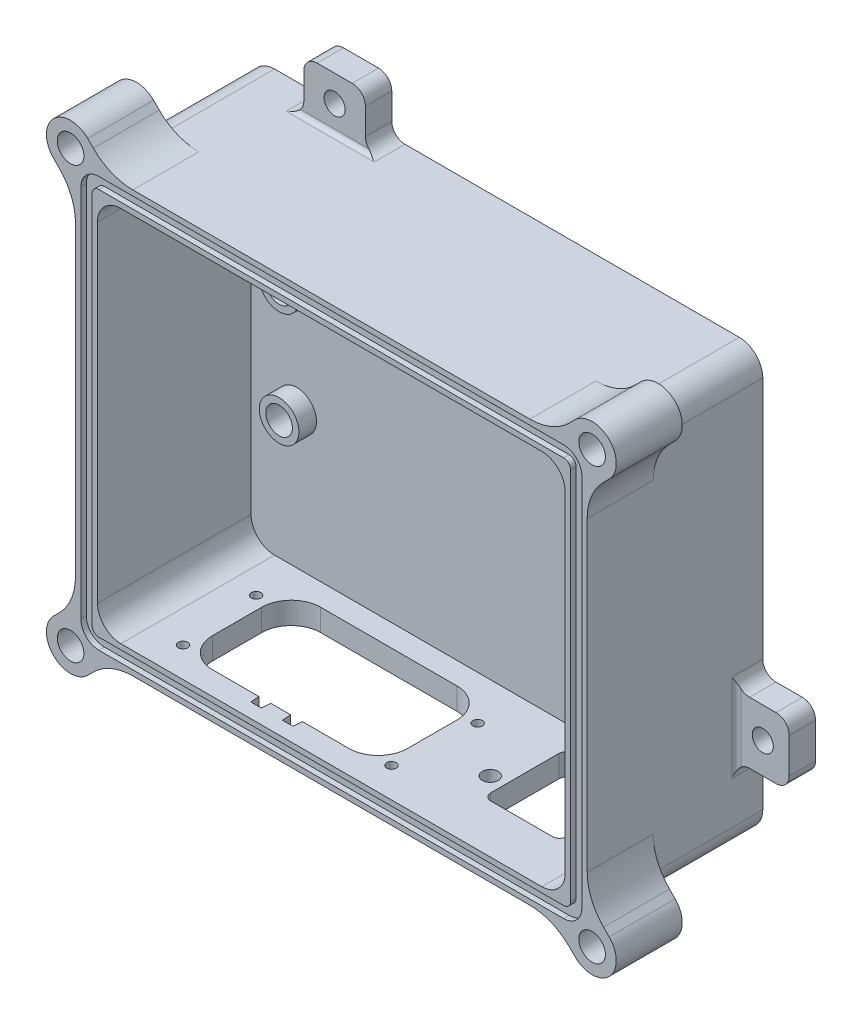
SolidWorks part; units mm, degrees
material "ABS"
ref_plane "X-Y Datum" through (0, 0, 0) normal (0, 0, 1) x (1, 0, 0)
ref_plane "X-Z Datum" through (0, 0, 0) normal (0, 1, 0) x (1, 0, 0)
ref_plane "Y-Z Datum" through (0, 0, 0) normal (1, 0, 0) x (0, 0, -1)
sketch "Sketch1" plane through (0, 0, 0) normal (0, 0, 1) x (1, 0, 0)
  line L1 (-53.1813, 42.8625) -> (53.1812, 42.8625)
  line L2 (-53.1813, 42.8625) -> (-53.1812, -42.8625)
  line L3 (-53.1812, -42.8625) -> (53.1813, -42.8625)
  line L4 (53.1812, 42.8625) -> (53.1813, -42.8625)
  line L5 (-53.1813, 42.8625) -> (53.1813, -42.8625) construction
  line L6 (-53.1812, -42.8625) -> (53.1812, 42.8625) construction
  point P0 (0, 0)
  dimension "D1" = 106.3625
  dimension "D2" = 85.725
extrude "Boss-Extrude1" add sketch "Sketch1" along normal blind 34.925
shell "Shell1" thickness 5 removed face at (0, 0, 34.925) outward yes
fillet "Fillet1" radius 5.334 8 edges at (-58.1812, -47.8625, 14.9625) (58.1813, -47.8625, 14.9625) (53.1812, 42.8625, 17.4625) (58.1812, 47.8625, 14.9625) (-58.1813, 47.8625, 14.9625) (-53.1813, 42.8625, 17.4625) (53.1813, -42.8625, 17.4625) (-53.1812, -42.8625, 17.4625)
sketch "Sketch2" plane through (0, 0, 34.925) normal (0, 0, 1) x (1, 0, 0)
  line L20 (-52.8472, -46.6452) -> (52.8472, -46.6452)
  line L21 (56.9639, -42.5285) -> (56.9639, 42.5285)
  line L22 (52.8472, 46.6452) -> (-52.8473, 46.6452)
  line L23 (-56.9639, 42.5285) -> (-56.9639, -42.5285)
  line L24 (-52.8472, -45.3625) -> (52.8473, -45.3625)
  line L25 (55.6812, -42.5285) -> (55.6812, 42.5285)
  line L26 (52.8472, 45.3625) -> (-52.8473, 45.3625)
  line L27 (-55.6812, 42.5285) -> (-55.6812, -42.5285)
  line L28 (-52.8472, -45.3625) -> (52.8473, -45.3625) construction
  line L29 (55.6812, -42.5285) -> (55.6812, 42.5285) construction
  line L30 (52.8472, 45.3625) -> (-52.8473, 45.3625) construction
  line L31 (-55.6812, 42.5285) -> (-55.6812, -42.5285) construction
  line L32 (-54.3986, 42.5285) -> (-54.3986, -42.5285)
  line L33 (-52.8472, -44.0798) -> (52.8472, -44.0798)
  line L34 (54.3986, -42.5285) -> (54.3986, 42.5285)
  line L35 (52.8472, 44.0798) -> (-52.8473, 44.0798)
  arc A16 (52.8472, -46.6452) -> (56.9639, -42.5285) centre (52.8473, -42.5285) ccw
  arc A17 (56.9639, 42.5285) -> (52.8472, 46.6452) centre (52.8472, 42.5285) ccw
  arc A18 (-52.8473, 46.6452) -> (-56.9639, 42.5285) centre (-52.8473, 42.5285) ccw
  arc A19 (-56.9639, -42.5285) -> (-52.8472, -46.6452) centre (-52.8472, -42.5285) ccw
  arc A20 (-55.6812, -42.5285) -> (-52.8472, -45.3625) centre (-52.8472, -42.5285) ccw
  arc A21 (52.8473, -45.3625) -> (55.6812, -42.5285) centre (52.8473, -42.5285) ccw
  arc A22 (55.6812, 42.5285) -> (52.8472, 45.3625) centre (52.8472, 42.5285) ccw
  arc A23 (-52.8473, 45.3625) -> (-55.6812, 42.5285) centre (-52.8473, 42.5285) ccw
  arc A24 (-55.6812, -42.5285) -> (-52.8472, -45.3625) centre (-52.8472, -42.5285) ccw construction
  arc A25 (52.8473, -45.3625) -> (55.6812, -42.5285) centre (52.8473, -42.5285) ccw construction
  arc A26 (55.6812, 42.5285) -> (52.8472, 45.3625) centre (52.8472, 42.5285) ccw construction
  arc A27 (-52.8473, 45.3625) -> (-55.6812, 42.5285) centre (-52.8473, 42.5285) ccw construction
  arc A28 (-52.8473, 44.0798) -> (-54.3986, 42.5285) centre (-52.8473, 42.5285) ccw
  arc A29 (-54.3986, -42.5285) -> (-52.8472, -44.0798) centre (-52.8472, -42.5285) ccw
  arc A30 (52.8472, -44.0798) -> (54.3986, -42.5285) centre (52.8473, -42.5285) ccw
  arc A31 (54.3986, 42.5285) -> (52.8472, 44.0798) centre (52.8472, 42.5285) ccw
  dimension "D4" = 2.5654
  dimension "D1" = 2.5
  dimension "D2" = 1.2827
  dimension "D3" = 1.2827
extrude "Cut-Extrude1" cut sketch "Sketch2" against normal blind 1.2446
sketch "Sketch4" plane through (0, 0, 34.925) normal (0, 0, 1) x (1, 0, 0)
  line L4 (58.1813, -42.5285) -> (58.1812, 42.5285) construction
  line L6 (47.8473, -37.5285) -> (59.2937, -48.975)
  line L7 (55.4046, -52.8641) -> (50.4031, -47.8625)
  line L8 (-52.8472, -47.8625) -> (52.8473, -47.8625) construction
  line L9 (63.1828, -45.0859) -> (58.1813, -40.0843)
  line L10 (-52.8472, -47.8625) -> (52.8473, -47.8625)
  line L11 (58.1813, -42.5285) -> (58.1812, 42.5285)
  arc A2 (47.8473, -42.8625) -> (53.1813, -37.5285) centre (47.8473, -37.5285) ccw construction
  circle A3 centre (59.2937, -48.975) radius 3.025
  circle A4 centre (59.2937, -48.975) radius 5.5
  arc A5 (52.8472, -46.6452) -> (56.9639, -42.5285) centre (52.8473, -42.5285) ccw construction
  arc A6 (52.8473, -47.8625) -> (58.1813, -42.5285) centre (52.8473, -42.5285) ccw construction
  arc A7 (58.1812, 42.5285) -> (52.8472, 47.8625) centre (52.8472, 42.5285) ccw construction
  arc A8 (52.8473, -47.8625) -> (58.1813, -42.5285) centre (52.8473, -42.5285) ccw
  arc A9 (58.1812, 42.5285) -> (52.8472, 47.8625) centre (52.8472, 42.5285) ccw
  point P14 (51.619, -41.3002)
  point P23 (55.7582, -45.4394)
  dimension "D1" = 11
  dimension "D2" = 6.05
  dimension "D4" = 5
extrude "Boss-Extrude2" add sketch "Sketch4" against normal blind 15 separate body contours A9 L11 | A9 | A8 A4 L9 L11 | A8 L10 L7 A4 | A8 A4 A3 | A3 | L11 region at (60.4186, -46.2593, 34.925) region at (57.6777, -45.1365, 34.925) region at (59.5123, -42.505, 34.925) region at (52.8237, -49.1935, 34.925)
sketch "Sketch5" plane through (0, 0, 34.925) normal (0, 0, 1) x (1, 0, 0)
  line L3 (-52.8472, -47.8625) -> (52.8473, -47.8625) construction
  line L4 (63.1828, -45.0859) -> (58.1813, -40.0843) construction
  line L5 (55.4046, -52.8641) -> (50.4031, -47.8625) construction
  line L6 (47.8473, -37.5285) -> (59.2937, -48.975) construction
  line L10 (-52.8472, -47.8625) -> (52.8473, -47.8625)
  line L11 (63.1828, -45.0859) -> (58.1813, -40.0843)
  line L12 (55.4046, -52.8641) -> (50.4031, -47.8625)
  line L13 (47.8473, -37.5285) -> (59.2937, -48.975)
  circle A1 centre (59.2937, -48.975) radius 3.025
  circle A2 centre (59.2937, -48.975) radius 3.025
  circle A7 centre (59.2937, -48.975) radius 5.5
  circle A8 centre (59.2937, -48.975) radius 5.5
  arc A9 (52.8473, -47.8625) -> (58.1813, -42.5285) centre (52.8473, -42.5285) ccw construction
  arc A11 (52.8473, -47.8625) -> (58.1813, -42.5285) centre (52.8473, -42.5285) ccw
  dimension "D1" = 0
  dimension "D4" = 0
extrude "Cut-Extrude4" cut sketch "Sketch5" against normal blind 8 contours A2 region at (60.4186, -46.2593, 34.925)
mirror "Mirror3" about plane through (0, 0, 0) normal (1, 0, 0) of bodies 107 106
mirror "Mirror7" about plane through (0, 0, 0) normal (0, 1, 0) of bodies 107 109
combine bodies "Combine3" operation type add bodies to combine 102 107 109 121 122
fillet "Fillet2" radius 12.7 8 edges at (-50.4031, -47.8625, 27.425) (-58.1813, -40.0843, 27.425) (50.4031, -47.8625, 27.425) (58.1813, -40.0843, 27.425) (-58.1813, 40.0843, 27.425) (-50.4031, 47.8625, 27.425) (50.4031, 47.8625, 27.425) (58.1813, 40.0843, 27.425)
sketch "Sketch13" plane through (0, -47.8625, 0) normal (0, -1, 0) x (1, 0, 0)
  line L0 (-12.3227, 29.1278) -> (-12.4976, 31.1278) construction
  line L1 (-12.4976, 31.1278) -> (-13.9477, 31.1278) construction
  line L2 (-13.9477, 31.1278) -> (-14.1227, 29.1278) construction
  line L3 (-19.6976, 31.1278) -> (-21.1477, 31.1278) construction
  line L4 (-21.1477, 31.1278) -> (-21.3227, 29.1278) construction
  line L5 (-19.5227, 29.1278) -> (-19.6976, 31.1278) construction
  line L6 (-21.3227, 29.1278) -> (-32.3227, 29.1278) construction
  line L7 (-38.5227, 22.9278) -> (-38.5227, 11.7278) construction
  line L8 (-32.3227, 5.5278) -> (-1.3227, 5.5278) construction
  line L9 (4.8773, 11.7278) -> (4.8773, 22.9278) construction
  line L10 (-1.3227, 29.1278) -> (-12.3227, 29.1278) construction
  line L11 (-14.1227, 29.1278) -> (-19.5227, 29.1278) construction
  line L52 (-12.3227, 29.1278) -> (-12.4976, 31.1278) construction
  line L53 (-12.4976, 31.1278) -> (-13.9477, 31.1278) construction
  line L54 (-13.9477, 31.1278) -> (-14.1227, 29.1278) construction
  line L55 (-19.6976, 31.1278) -> (-21.1477, 31.1278) construction
  line L67 (24.0563, 22.2478) -> (24.0563, 6.6978) construction
  line L80 (-21.1477, 31.1278) -> (-21.3227, 29.1278) construction
  line L81 (-19.5227, 29.1278) -> (-19.6976, 31.1278) construction
  line L82 (-21.3227, 29.1278) -> (-32.3227, 29.1278) construction
  line L83 (-38.5227, 22.9278) -> (-38.5227, 11.7278) construction
  line L84 (-32.3227, 5.5278) -> (-1.3227, 5.5278) construction
  line L85 (4.8773, 11.7278) -> (4.8773, 22.9278) construction
  line L86 (-1.3227, 29.1278) -> (-12.3227, 29.1278) construction
  line L87 (-14.1227, 29.1278) -> (-19.5227, 29.1278) construction
  line L88 (-11.8645, 29.6278) -> (-12.0395, 31.6278)
  line L89 (-12.0395, 31.6278) -> (-14.4059, 31.6278)
  line L90 (-14.4059, 31.6278) -> (-14.5808, 29.6278)
  line L91 (-14.5808, 29.6278) -> (-19.0645, 29.6278)
  line L92 (-19.0645, 29.6278) -> (-19.2395, 31.6278)
  line L93 (-19.2395, 31.6278) -> (-21.6059, 31.6278)
  line L94 (-21.6059, 31.6278) -> (-21.7808, 29.6278)
  line L95 (-21.7808, 29.6278) -> (-32.3227, 29.6278)
  line L96 (-39.0227, 22.9278) -> (-39.0227, 11.7278)
  line L97 (-32.3227, 5.0278) -> (-1.3227, 5.0278)
  line L98 (5.3773, 11.7278) -> (5.3773, 22.9278)
  line L99 (-1.3227, 29.6278) -> (-11.8645, 29.6278)
  line L100 (25.1563, 5.5978) -> (39.2063, 5.5978) construction
  line L101 (40.3063, 6.6978) -> (40.3063, 22.2478) construction
  line L102 (39.2063, 23.3478) -> (25.1563, 23.3478) construction
  line L103 (24.0563, 22.2478) -> (24.0563, 6.6978) construction
  line L104 (25.1563, 5.5978) -> (39.2063, 5.5978) construction
  line L105 (40.3063, 6.6978) -> (40.3063, 22.2478) construction
  line L106 (39.2063, 23.3478) -> (25.1563, 23.3478) construction
  line L107 (23.5563, 22.2478) -> (23.5563, 6.6978)
  line L124 (25.1563, 5.0978) -> (39.2063, 5.0978)
  line L125 (40.8063, 6.6978) -> (40.8063, 22.2478)
  line L126 (39.2063, 23.8478) -> (25.1563, 23.8478)
  arc A0 (24.0563, 6.6978) -> (25.1563, 5.5978) centre (25.1563, 6.6978) ccw construction
  arc A1 (39.2063, 5.5978) -> (40.3063, 6.6978) centre (39.2063, 6.6978) ccw construction
  arc A2 (40.3063, 22.2478) -> (39.2063, 23.3478) centre (39.2063, 22.2478) ccw construction
  arc A3 (25.1563, 23.3478) -> (24.0563, 22.2478) centre (25.1563, 22.2478) ccw construction
  arc A12 (24.0563, 6.6978) -> (25.1563, 5.5978) centre (25.1563, 6.6978) ccw construction
  arc A13 (39.2063, 5.5978) -> (40.3063, 6.6978) centre (39.2063, 6.6978) ccw construction
  arc A14 (40.3063, 22.2478) -> (39.2063, 23.3478) centre (39.2063, 22.2478) ccw construction
  arc A15 (25.1563, 23.3478) -> (24.0563, 22.2478) centre (25.1563, 22.2478) ccw construction
  arc A24 (23.5563, 6.6978) -> (25.1563, 5.0978) centre (25.1563, 6.6978) ccw
  arc A25 (39.2063, 5.0978) -> (40.8063, 6.6978) centre (39.2063, 6.6978) ccw
  arc A26 (40.8063, 22.2478) -> (39.2063, 23.8478) centre (39.2063, 22.2478) ccw
  arc A27 (25.1563, 23.8478) -> (23.5563, 22.2478) centre (25.1563, 22.2478) ccw
  spline S0 degree 3 poles (-32.3227, 29.1278) (-35.9545, 29.1278) (-38.5227, 26.5597) (-38.5227, 22.9278) knots 0 0 0 0 1 1 1 1 weights 1 0.804738 0.804738 1 construction
  spline S1 degree 3 poles (-38.5227, 11.7278) (-38.5227, 8.0959) (-35.9545, 5.5278) (-32.3227, 5.5278) knots 0 0 0 0 1 1 1 1 weights 1 0.804738 0.804738 1 construction
  spline S2 degree 3 poles (-1.3227, 5.5278) (2.3092, 5.5278) (4.8773, 8.0959) (4.8773, 11.7278) knots 0 0 0 0 1 1 1 1 weights 1 0.804738 0.804738 1 construction
  spline S3 degree 3 poles (4.8773, 22.9278) (4.8773, 26.5597) (2.3092, 29.1278) (-1.3227, 29.1278) knots 0 0 0 0 1 1 1 1 weights 1 0.804738 0.804738 1 construction
  spline S4 degree 3 poles (-32.3227, 29.1278) (-35.9545, 29.1278) (-38.5227, 26.5597) (-38.5227, 22.9278) knots 0 0 0 0 1 1 1 1 weights 1 0.804738 0.804738 1 construction
  spline S5 degree 3 poles (-38.5227, 11.7278) (-38.5227, 8.0959) (-35.9545, 5.5278) (-32.3227, 5.5278) knots 0 0 0 0 1 1 1 1 weights 1 0.804738 0.804738 1 construction
  spline S6 degree 3 poles (-1.3227, 5.5278) (2.3092, 5.5278) (4.8773, 8.0959) (4.8773, 11.7278) knots 0 0 0 0 1 1 1 1 weights 1 0.804738 0.804738 1 construction
  spline S7 degree 3 poles (4.8773, 22.9278) (4.8773, 26.5597) (2.3092, 29.1278) (-1.3227, 29.1278) knots 0 0 0 0 1 1 1 1 weights 1 0.804738 0.804738 1 construction
  spline S8 degree 1 poles (-32.3227, 29.6278) (-39.0227, 22.9278) knots 0 0 1 1 construction
  spline S9 degree 1 poles (-39.0227, 11.7278) (-32.3227, 5.0278) knots 0 0 1 1 construction
  spline S10 degree 1 poles (-1.3227, 5.0278) (5.3773, 11.7278) knots 0 0 1 1 construction
  spline S11 degree 1 poles (5.3773, 22.9278) (-1.3227, 29.6278) knots 0 0 1 1 construction
  spline S12 degree 3 poles (-32.3227, 29.6278) (-32.7308, 29.6278) (-33.5306, 29.5573) (-35.22, 29.0854) (-37.2004, 27.8055) (-38.4803, 25.8252) (-38.9522, 24.1358) (-39.0227, 23.3359) (-39.0227, 22.9278) knots 0 0 0 0 0.125 0.25 0.5 0.75 0.875 1 1 1 1
  spline S13 degree 3 poles (-39.0227, 11.7278) (-39.0227, 11.3197) (-38.9522, 10.5199) (-38.4803, 8.8305) (-37.2004, 6.8501) (-35.22, 5.5702) (-33.5306, 5.0983) (-32.7308, 5.0278) (-32.3227, 5.0278) knots 0 0 0 0 0.125 0.25 0.5 0.75 0.875 1 1 1 1
  spline S14 degree 3 poles (-1.3227, 5.0278) (-0.9146, 5.0278) (-0.1147, 5.0983) (1.5747, 5.5702) (3.555, 6.8501) (4.8349, 8.8305) (5.3068, 10.5199) (5.3773, 11.3197) (5.3773, 11.7278) knots 0 0 0 0 0.125 0.25 0.5 0.75 0.875 1 1 1 1
  spline S15 degree 3 poles (5.3773, 22.9278) (5.3773, 23.3359) (5.3068, 24.1358) (4.8349, 25.8252) (3.555, 27.8055) (1.5747, 29.0854) (-0.1147, 29.5573) (-0.9146, 29.6278) (-1.3227, 29.6278) knots 0 0 0 0 0.125 0.25 0.5 0.75 0.875 1 1 1 1
  spline S16 degree 3 poles (-43.1077, 10.0278) (-43.1077, 12.1978) (-40.9377, 12.1978) (-40.9377, 10.0278) knots 0 0 0 0 1 1 1 1 weights 1 0.333333 0.333333 1 construction
  spline S17 degree 3 poles (-40.9377, 10.0278) (-40.9377, 7.8578) (-43.1077, 7.8578) (-43.1077, 10.0278) knots 0 0 0 0 1 1 1 1 weights 1 0.333333 0.333333 1 construction
  spline S18 degree 3 poles (-41.6077, 28.1278) (-41.6077, 30.2978) (-39.4377, 30.2978) (-39.4377, 28.1278) knots 0 0 0 0 1 1 1 1 weights 1 0.333333 0.333333 1 construction
  spline S19 degree 3 poles (-39.4377, 28.1278) (-39.4377, 25.9578) (-41.6077, 25.9578) (-41.6077, 28.1278) knots 0 0 0 0 1 1 1 1 weights 1 0.333333 0.333333 1 construction
  spline S20 degree 3 poles (-43.1077, 10.0278) (-43.1077, 12.1978) (-40.9377, 12.1978) (-40.9377, 10.0278) knots 0 0 0 0 1 1 1 1 weights 1 0.333333 0.333333 1
  spline S21 degree 3 poles (-40.9377, 10.0278) (-40.9377, 7.8578) (-43.1077, 7.8578) (-43.1077, 10.0278) knots 0 0 0 0 1 1 1 1 weights 1 0.333333 0.333333 1
  spline S22 degree 3 poles (-41.6077, 28.1278) (-41.6077, 30.2978) (-39.4377, 30.2978) (-39.4377, 28.1278) knots 0 0 0 0 1 1 1 1 weights 1 0.333333 0.333333 1
  spline S23 degree 3 poles (-39.4377, 28.1278) (-39.4377, 25.9578) (-41.6077, 25.9578) (-41.6077, 28.1278) knots 0 0 0 0 1 1 1 1 weights 1 0.333333 0.333333 1
  spline S24 degree 3 poles (7.9623, 28.1278) (7.9623, 25.9578) (5.7923, 25.9578) (5.7923, 28.1278) knots 0 0 0 0 1 1 1 1 weights 1 0.333333 0.333333 1 construction
  spline S25 degree 3 poles (5.7923, 28.1278) (5.7923, 30.2978) (7.9623, 30.2978) (7.9623, 28.1278) knots 0 0 0 0 1 1 1 1 weights 1 0.333333 0.333333 1 construction
  spline S26 degree 3 poles (7.9623, 28.1278) (7.9623, 25.9578) (5.7923, 25.9578) (5.7923, 28.1278) knots 0 0 0 0 1 1 1 1 weights 1 0.333333 0.333333 1
  spline S27 degree 3 poles (5.7923, 28.1278) (5.7923, 30.2978) (7.9623, 30.2978) (7.9623, 28.1278) knots 0 0 0 0 1 1 1 1 weights 1 0.333333 0.333333 1
  spline S28 degree 3 poles (9.4623, 10.0278) (9.4623, 7.8578) (7.2923, 7.8578) (7.2923, 10.0278) knots 0 0 0 0 1 1 1 1 weights 1 0.333333 0.333333 1 construction
  spline S29 degree 3 poles (7.2923, 10.0278) (7.2923, 12.1978) (9.4623, 12.1978) (9.4623, 10.0278) knots 0 0 0 0 1 1 1 1 weights 1 0.333333 0.333333 1 construction
  spline S30 degree 3 poles (7.2923, 10.0278) (7.2923, 12.1978) (9.4623, 12.1978) (9.4623, 10.0278) knots 0 0 0 0 1 1 1 1 weights 1 0.333333 0.333333 1
  spline S31 degree 3 poles (9.4623, 10.0278) (9.4623, 7.8578) (7.2923, 7.8578) (7.2923, 10.0278) knots 0 0 0 0 1 1 1 1 weights 1 0.333333 0.333333 1
  point P47 (20.1813, 18.9728)
  point P48 (44.1813, 9.9728)
  dimension "D1" = 0.5
  dimension "D2" = 0.5
extrude "Cut-Extrude6" cut sketch "Sketch13" against normal blind 5 contours L126 A27 L107 A24 L124 A25 L125 A26 | L98 S15 L99 L88 L89 L90 L91 L92 L93 L94 L95 S12 L96 S13 L97 S14 | S27 S26 | S31 S30 | S23 S22 | S21 S20 region at (-16.8227, -47.8625, 17.4547) region at (32.1813, -47.8625, 14.4728) region at (-42.0227, -47.8625, 10.0278) region at (-40.5227, -47.8625, 28.1278) region at (6.8773, -47.8625, 28.1278) region at (8.3773, -47.8625, 10.0278)
hole_wizard "M3 Clearance Hole1" positions "Sketch17" profile "Sketch15" hole size "M3" standard "ANSI Metric"
sketch "Sketch17" plane through (0, -47.8625, 0) normal (0, -1, 0) x (-1, 0, 0)
  point P10 (-20.1813, -18.9728)
  point P13 (-44.1813, -9.9728)
sketch "Sketch15" plane through (20.1813, -47.8625, 18.9728) normal (1, 0, 0) x (0, 0, -1)
  line L0 (0, 0) -> (0, 6.0815)
  line L1 (0, 6.0815) -> (1.8, 5)
  line L2 (1.8, 5) -> (1.8, 0)
  line L5 (1.8, 0) -> (0, 0)
  line L10 (0, 6.0815) -> (-1.8, 5) construction
  line L11 (0, -6.35) -> (0, 107.95) construction
  dimension "Hole Dia." = 3.6
  dimension "Hole Depth" = 5
  dimension "Drill Angle" = 118
sketch "Sketch18" plane through (0, 0, 0) normal (0, 0, 1) x (1, 0, 0)
  circle A0 centre (-42.8028, 14.0785) radius 3.025
  circle A1 centre (-42.8028, -11.8295) radius 3.025
  circle A2 centre (28.9332, -12.9535) radius 3.025
  circle A3 centre (28.9332, 14.9865) radius 3.025
  circle A4 centre (-42.8028, 14.0785) radius 4.5
  circle A5 centre (-42.8028, -11.8295) radius 4.5
  circle A6 centre (28.9332, 14.9865) radius 4.5
  circle A7 centre (28.9332, -12.9535) radius 4.5
  point P0 (-42.8028, 14.0785)
  point P1 (-42.8028, -11.8295)
  point P3 (28.9332, -12.9535)
  point P5 (28.9332, 14.9865)
  dimension "D1" = 6.05
  dimension "D2" = 9
extrude "Boss-Extrude3" add sketch "Sketch18" along normal blind 4
sketch "Sketch19" plane through (0, 0, 0) normal (0, 0, 1) x (1, 0, 0)
  circle A0 centre (28.9332, 14.9865) radius 3.025 construction
  circle A1 centre (28.9332, -12.9535) radius 3.025 construction
  circle A2 centre (-42.8028, -11.8295) radius 3.025 construction
  circle A3 centre (-42.8028, 14.0785) radius 3.025 construction
  circle A4 centre (28.9332, 14.9865) radius 3.025
  circle A5 centre (28.9332, -12.9535) radius 3.025
  circle A6 centre (-42.8028, -11.8295) radius 3.025
  circle A7 centre (-42.8028, 14.0785) radius 3.025
extrude "Cut-Extrude7" cut sketch "Sketch19" against normal blind 1.5
sketch "Sketch20" plane through (0, 0, -5) normal (0, 0, -1) x (-1, 0, 0)
  line L0 (-45.1426, 47.8625) -> (45.1426, 47.8625) construction
  line L1 (40.1812, 47.8625) -> (26.1813, 47.8625)
  line L2 (40.1812, 47.8625) -> (40.1812, 59.8625)
  line L3 (40.1812, 59.8625) -> (26.1813, 59.8625)
  line L4 (26.1813, 47.8625) -> (26.1813, 59.8625)
  line L5 (-58.1813, -34.8238) -> (-58.1812, 34.8238) construction
  line L6 (-58.1813, -15.8625) -> (-70.1813, -15.8625)
  line L7 (-58.1813, -15.8625) -> (-58.1813, -29.8625)
  line L8 (-58.1813, -29.8625) -> (-70.1813, -29.8625)
  line L9 (-70.1813, -15.8625) -> (-70.1813, -29.8625)
  line L10 (40.1812, 59.8625) -> (26.1813, 47.8625) construction
  line L11 (-58.1813, -15.8625) -> (-70.1813, -29.8625) construction
  line L12 (58.1813, 34.8238) -> (58.1812, -34.8238) construction
  line L13 (45.1426, -47.8625) -> (-45.1426, -47.8625) construction
  circle A0 centre (33.1813, 53.8625) radius 2 construction
  circle A1 centre (-64.1813, -22.8625) radius 2 construction
  dimension "D1" = 4
  dimension "D2" = 12
  dimension "D3" = 14
  dimension "D4" = 25
  dimension "D5" = 25
extrude "Boss-Extrude4" add sketch "Sketch20" against normal blind 6
hole_wizard "M4 Clearance Hole1" positions "Sketch23" profile "Sketch22" hole size "M4" standard "ANSI Metric" end condition through all
sketch "Sketch23" plane through (0, 0, 1) normal (0, 0, 1) x (1, 0, 0)
  point P0 (-33.1813, 53.8625)
  point P3 (64.1813, -22.8625)
sketch "Sketch22" plane through (-33.1813, 53.8625, 1) normal (1, 0, 0) x (0, -1, 0)
  line L0 (0, 0) -> (0, 6)
  line L1 (0, 6) -> (2.4, 6)
  line L2 (2.4, 6) -> (2.4, 0)
  line L5 (2.4, 0) -> (0, 0)
  line L11 (0, -6.35) -> (0, 107.95) construction
  dimension "Thru Hole Dia." = 4.8
  dimension "Thru Hole Depth" = 6
fillet "Fillet3" radius 3 8 edges at (-40.1812, 59.8625, -2) (-26.1813, 59.8625, -2) (-26.1813, 47.8625, -2) (-40.1812, 47.8625, -2) (70.1813, -29.8625, -2) (70.1813, -15.8625, -2) (58.1813, -15.8625, -2) (58.1813, -29.8625, -2)
fillet "Fillet4" radius 1 2 edges at (58.1813, -22.8625, 1) (-33.1813, 47.8625, 1)
